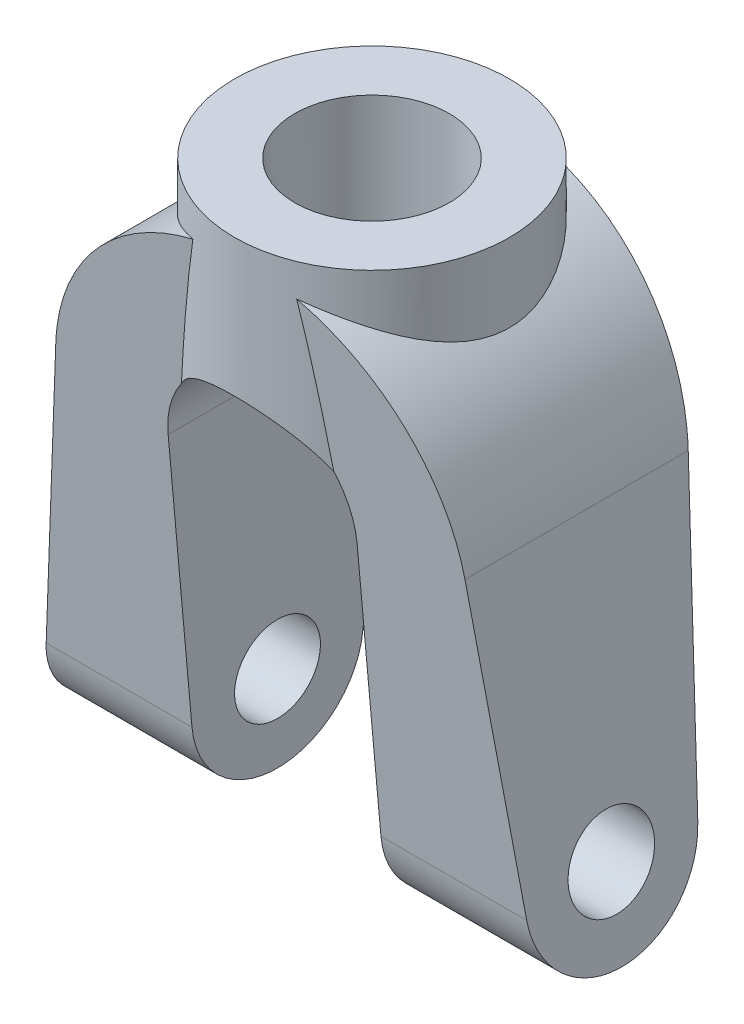
SolidWorks part; units mm, degrees
ref_plane "Front Plane" through (0, 0, 0) normal (0, 0, 1) x (1, 0, 0)
ref_plane "Top Plane" through (0, 0, 0) normal (0, 1, 0) x (1, 0, 0)
ref_plane "Right Plane" through (0, 0, 0) normal (1, 0, 0) x (0, 0, -1)
sketch "Sketch1" plane through (0, 0, 0) normal (0, 0, 1) x (1, 0, 0)
  line L0 (0, 0) -> (0, 40) construction
  line L1 (11, 40) -> (11, 0)
  line L2 (11, 0) -> (29.0916, 0)
  line L3 (29.0916, 0) -> (23.8211, 42.9249)
  line L4 (-29.0916, 0) -> (-23.8211, 42.9249)
  line L5 (-11, 0) -> (-29.0916, 0)
  line L6 (-11, 40) -> (-11, 0)
  circle A0 centre (0, 40) radius 24
  circle A1 centre (0, 40) radius 11
  point P7 (0, 0)
  point P10 (0, 0)
  point P11 (20.1823, 26.4793)
  point P12 (0, 0)
  dimension "D1" = 48
  dimension "D2" = 22
  dimension "D3" = 40
  dimension "D4" = 7
extrude "Boss-Extrude2" add sketch "Sketch1" along normal mid plane 40 contours A1 L1 A0 L6 | A0 L1 L2 L3 | A0 L4 L5 L6 region at (0, 51.6602, 0) region at (20.0594, 13.106, 0) region at (-20.0594, 13.106, 0)
sketch "Sketch3" plane through (0, 0, 0) normal (1, 0, 0) x (0, 0, -1)
  line L0 (-14.8862, 64) -> (-9.96, 9.1062)
  line L1 (20, 64) -> (-20, 64) construction
  line L2 (9.96, 9.1062) -> (14.8862, 64)
  line L3 (14.8862, 64) -> (-14.8862, 64)
  line L4 (0, 5.3115) -> (0, 57.2028) construction
  line L5 (0, 5.3115) -> (0, 0) construction
  line L7 (-20, 0) -> (20, 0) construction
  circle A1 centre (0, 10) radius 5
  arc A2 (-9.96, 9.1062) -> (9.96, 9.1062) centre (0, 10) ccw
  point P4 (0, 0)
  point P14 (0, 0)
  point P17 (0, 9.7879)
  dimension "D1" = 10
  dimension "D2" = 20
extrude "Cut-Extrude5" cut sketch "Sketch3" against normal through all both and the other way through all flip side to cut
sketch "Sketch4" plane through (0, 0, 0) normal (0, 1, 0) x (1, 0, 0)
  circle A0 centre (0, 0) radius 16
  circle A1 centre (0, 0) radius 9
  dimension "D1" = 32
  dimension "D2" = 18
extrude "Boss-Extrude3" add sketch "Sketch4" against normal up to vertex (-40 mm away) from offset 67 up to point (11, 40, 12.7324)
extrude "Cut-Extrude7" cut sketch "Sketch4<4>" along normal blind 70 contours A1 region at (0, 0, 0)
sketch "Sketch4<4>" plane through (0, 0, 0) normal (0, 1, 0) x (1, 0, 0) same geometry as "Sketch4"
sketch "Sketch5" plane through (0, 0, 0) normal (0, 0, 1) x (1, 0, 0)
  line L0 (-11, 40) -> (11, 40) construction
  line L1 (-11, 40) -> (11, 40)
  arc A0 (11, 40) -> (8.8701, 46.5055) centre (0, 40) ccw construction
  arc A1 (-8.8701, 46.5055) -> (-11, 40) centre (0, 40) ccw construction
  arc A2 (11, 40) -> (8.8701, 46.5055) centre (0, 40) ccw
  arc A3 (8.8701, 46.5055) -> (-11, 40) centre (0, 40) ccw
  point P6 (0, 0)
  point P7 (8.8701, 47.4855)
extrude "Cut-Extrude8" cut sketch "Sketch5" against normal through all both and the other way through all
